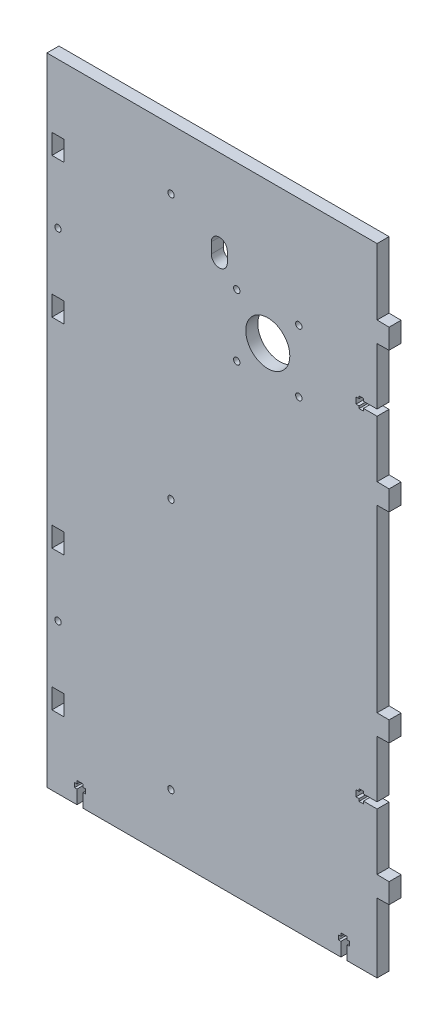
SolidWorks part; units mm, degrees
material "Клен"
ref_plane "Front" through (0, 0, 0) normal (0, 0, 1) x (1, 0, 0)
ref_plane "Top" through (0, 0, 0) normal (0, 1, 0) x (1, 0, 0)
ref_plane "Right" through (0, 0, 0) normal (1, 0, 0) x (0, 0, -1)
sketch "Эскиз1" plane through (0, 0, 0) normal (0, 0, 1) x (1, 0, 0)
  line L0 (995.8606, 795.6649) -> (995.8606, 790.382)
  line L1 (975.7199, 850.9685) -> (975.7199, 499.7864) construction
  line L2 (1003.8606, 790.382) -> (1003.8606, 795.6649)
  line L16 (922.3199, 553.2385) -> (922.3199, 563.2385)
  line L17 (916.2199, 553.2385) -> (922.3199, 553.2385)
  line L18 (916.2199, 563.2385) -> (916.2199, 553.2385)
  line L19 (922.3199, 563.2385) -> (916.2199, 563.2385)
  line L20 (916.2199, 623.2385) -> (922.3199, 623.2385)
  line L21 (922.3199, 623.2385) -> (922.3199, 633.2385)
  line L22 (922.3199, 633.2385) -> (916.2199, 633.2385)
  line L23 (916.2199, 633.2385) -> (916.2199, 623.2385)
  line L24 (916.2199, 723.2385) -> (922.3199, 723.2385)
  line L25 (922.3199, 723.2385) -> (922.3199, 733.2385)
  line L26 (916.2199, 733.2385) -> (916.2199, 723.2385)
  line L27 (922.3199, 733.2385) -> (916.2199, 733.2385)
  line L28 (922.3199, 793.2385) -> (922.3199, 803.2385)
  line L29 (922.3199, 803.2385) -> (916.2199, 803.2385)
  line L30 (916.2199, 803.2385) -> (916.2199, 793.2385)
  line L31 (916.2199, 793.2385) -> (922.3199, 793.2385)
  line L32 (978.7199, 858.5777) -> (978.7199, 499.7864) construction
  line L33 (1078.7199, 858.5777) -> (1078.7199, 499.7864) construction
  line L34 (1078.7199, 623.0385) -> (1084.7199, 623.1385)
  line L35 (1068.2199, 764.6885) -> (1069.7199, 764.6885)
  line L36 (1084.7199, 553.1385) -> (1084.7199, 563.1385)
  line L37 (1071.9199, 591.5885) -> (1071.9199, 590.3885)
  line L38 (1071.9199, 761.5885) -> (1071.9199, 760.3885)
  line L39 (1071.9199, 765.8885) -> (1071.9199, 764.6885)
  line L40 (1084.7199, 793.1385) -> (1084.7199, 803.1385)
  line L41 (1084.7199, 723.1385) -> (1084.7199, 733.1385)
  line L42 (1068.2199, 761.5885) -> (1068.2199, 764.6885)
  line L43 (1069.7199, 590.3885) -> (1069.7199, 591.5885)
  line L44 (1068.2199, 591.5885) -> (1068.2199, 594.6885)
  line L45 (1084.7199, 733.1385) -> (1078.7199, 733.2385)
  line L46 (1084.7199, 633.1385) -> (1078.7199, 633.2385)
  line L47 (1078.7199, 633.2385) -> (1078.7199, 723.0385)
  line L48 (1084.7199, 803.1385) -> (1078.7199, 803.2385)
  line L49 (1071.9199, 595.8885) -> (1071.9199, 594.6885)
  line L50 (1078.7199, 793.0385) -> (1084.7199, 793.1385)
  line L51 (1078.7199, 733.2385) -> (1078.7199, 761.5885)
  line L52 (1068.2199, 594.6885) -> (1069.7199, 594.6885)
  line L53 (1071.9199, 760.3885) -> (1069.7199, 760.3885)
  line L54 (1069.7199, 761.5885) -> (1068.2199, 761.5885)
  line L55 (1069.7199, 765.8885) -> (1071.9199, 765.8885)
  line L112 (931.8199, 525.2362) -> (931.8199, 518.4362)
  line L113 (931.8199, 518.4362) -> (978.7199, 518.4362)
  line L155 (978.7199, 836.3385) -> (913.7199, 836.3385)
  line L156 (913.7199, 836.3385) -> (913.7199, 518.4362)
  line L157 (913.7199, 518.4362) -> (928.7199, 518.4362)
  line L158 (928.7199, 518.4362) -> (928.7199, 525.2362)
  line L159 (928.7199, 525.2362) -> (927.5199, 525.2362)
  line L160 (927.5199, 525.2362) -> (927.5199, 527.4362)
  line L161 (927.5199, 527.4362) -> (928.7199, 527.4362)
  line L162 (928.7199, 527.4362) -> (928.7199, 528.9362)
  line L163 (928.7199, 528.9362) -> (931.8199, 528.9362)
  line L164 (931.8199, 528.9362) -> (931.8199, 527.4362)
  line L165 (931.8199, 527.4362) -> (933.0199, 527.4362)
  line L166 (933.0199, 527.4362) -> (933.0199, 525.2362)
  line L167 (933.0199, 525.2362) -> (931.8199, 525.2362)
  line L168 (1069.7199, 594.6885) -> (1069.7199, 595.8885)
  line L169 (1078.7199, 594.6885) -> (1078.7199, 623.0385)
  line L170 (1071.9199, 764.6885) -> (1078.7199, 764.6885)
  line L171 (1084.7199, 563.1385) -> (1078.7199, 563.2385)
  line L172 (1084.7199, 623.1385) -> (1084.7199, 633.1385)
  line L173 (1069.7199, 764.6885) -> (1069.7199, 765.8885)
  line L174 (1078.7199, 553.0385) -> (1084.7199, 553.1385)
  line L175 (1078.7199, 563.2385) -> (1078.7199, 591.5885)
  line L176 (1078.7199, 761.5885) -> (1071.9199, 761.5885)
  line L177 (1078.7199, 518.4362) -> (1078.7199, 553.0385)
  line L178 (1069.7199, 591.5885) -> (1068.2199, 591.5885)
  line L179 (1069.7199, 595.8885) -> (1071.9199, 595.8885)
  line L180 (1069.7199, 760.3885) -> (1069.7199, 761.5885)
  line L181 (1078.7199, 591.5885) -> (1071.9199, 591.5885)
  line L182 (1071.9199, 594.6885) -> (1078.7199, 594.6885)
  line L183 (1078.7199, 803.2385) -> (1078.7199, 836.3385)
  line L184 (1071.9199, 590.3885) -> (1069.7199, 590.3885)
  line L185 (1078.7199, 723.0385) -> (1084.7199, 723.1385)
  line L186 (1078.7199, 764.6885) -> (1078.7199, 793.0385)
  line L187 (978.7199, 836.3385) -> (1078.7199, 836.3385)
  line L188 (978.7199, 518.4362) -> (1060.6199, 518.4362)
  line L189 (1059.4199, 527.4362) -> (1060.6199, 527.4362)
  line L190 (1060.6199, 518.4362) -> (1060.6199, 525.2362)
  line L191 (1064.9199, 525.2362) -> (1063.7199, 525.2362)
  line L192 (1060.6199, 527.4362) -> (1060.6199, 528.9362)
  line L193 (1060.6199, 528.9362) -> (1063.7199, 528.9362)
  line L194 (1060.6199, 525.2362) -> (1059.4199, 525.2362)
  line L195 (1063.7199, 525.2362) -> (1063.7199, 518.4362)
  line L196 (1063.7199, 528.9362) -> (1063.7199, 527.4362)
  line L197 (1063.7199, 527.4362) -> (1064.9199, 527.4362)
  line L198 (1059.4199, 525.2362) -> (1059.4199, 527.4362)
  line L199 (1064.9199, 527.4362) -> (1064.9199, 525.2362)
  line L200 (1063.7199, 518.4362) -> (1078.7199, 518.4362)
  circle A2 centre (919.2699, 593.2385) radius 1.6
  circle A3 centre (919.2699, 763.2385) radius 1.6
  circle A5 centre (975.7199, 806.3385) radius 1.6
  circle A6 centre (975.7199, 674.1385) radius 1.6
  circle A7 centre (975.7199, 548.4385) radius 1.6
  circle A8 centre (1008.611, 781.3885) radius 1.6
  circle A9 centre (1008.611, 750.3885) radius 1.6
  circle A10 centre (1024.111, 765.8885) radius 11
  circle A11 centre (1039.611, 750.3885) radius 1.6
  circle A12 centre (1039.611, 781.3885) radius 1.6
  arc A13 (995.8606, 790.382) -> (1003.8606, 790.382) centre (999.8606, 790.382) ccw
  arc A14 (1003.8606, 795.6649) -> (995.8606, 795.6649) centre (999.8606, 795.6649) ccw
  dimension "D13" = 3.2
  dimension "D14" = 3.2
  dimension "D15" = 3.2
  dimension "D2" = 100
  dimension "D3" = 65
  dimension "D4" = 15
  dimension "D12" = 103
extrude "Бобышка-Вытянуть1" add sketch "Эскиз1" along normal blind 6
